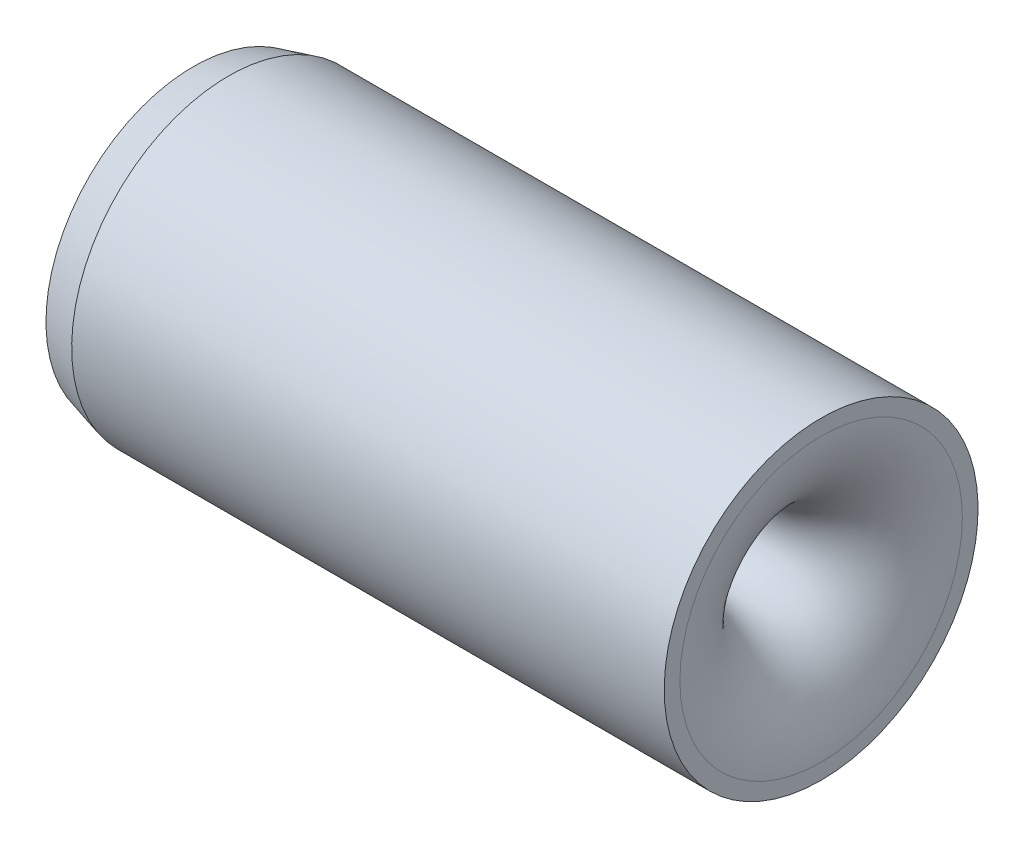
SolidWorks part; units mm, degrees
ref_plane "Front" through (0, 0, 0) normal (0, 0, 1) x (1, 0, 0)
ref_plane "Top" through (0, 0, 0) normal (0, 1, 0) x (1, 0, 0)
ref_plane "Right" through (0, 0, 0) normal (1, 0, 0) x (0, 0, -1)
sketch "Sketch1" plane through (0, 0, 0) normal (0, 0, 1) x (1, 0, 0)
  line L0 (-3, 0) -> (3, 0) construction
  line L1 (-3, 1.41) -> (-2.6641, 1.5)
  line L2 (-2.6641, 1.5) -> (3, 1.5)
  line L3 (-3, 1.41) -> (-3, 1.35)
  line L4 (-2, 0.35) -> (2, 0.35)
  line L5 (3, 1.5) -> (3, 1.35)
  arc A0 (2, 0.35) -> (3, 1.35) centre (2, 1.35) ccw
  arc A1 (-3, 1.35) -> (-2, 0.35) centre (-2, 1.35) ccw
  point P2 (0, 0)
  point P11 (3, 0.35)
  point P14 (-3, 0.35)
  dimension "D2" = 1
  dimension "D1" = 15
revolve "Revolve1" add sketch "Sketch1" angle 360 about L0
ref_axis "Center Axis 1" through (2, 0, 0) along (-1, 0, 0)
ref_plane "Contact Plane 1" through (-3, 0, 0) normal (-1, 0, 0) x (0, 0, 1)
ref_plane "Contact Plane 2" through (3, 0, 0) normal (1, 0, 0) x (0, 0, -1)
equation "\"T@Sketch1\"=\"OD@Sketch1\"*.03"
equation "\"D2@Sketch1\"=\"R@Sketch1\""
